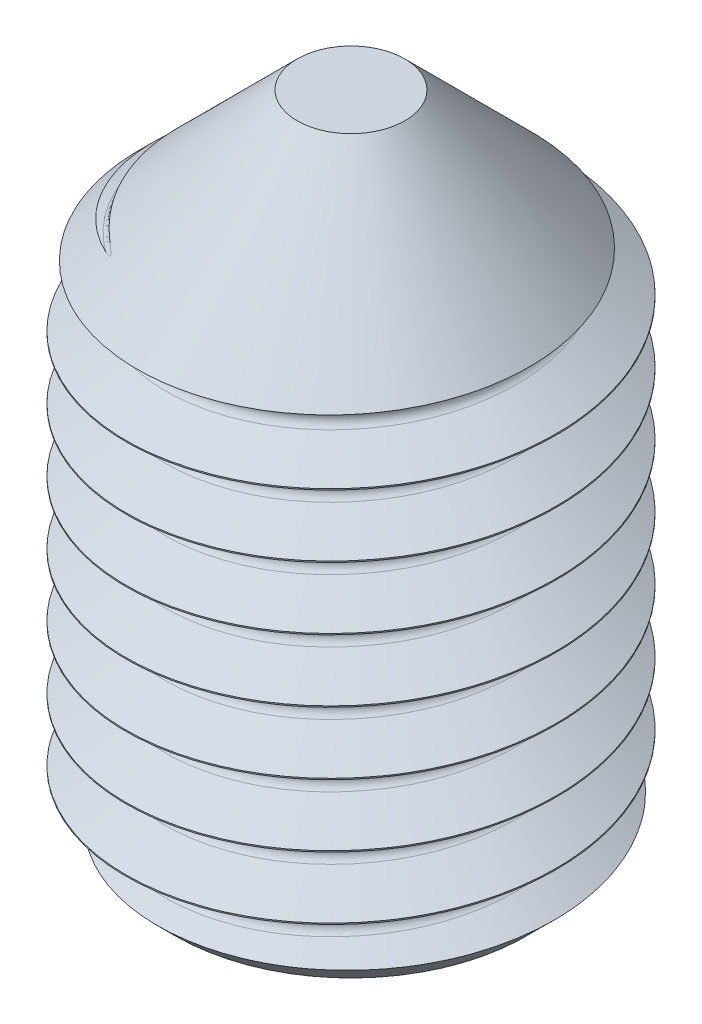
SolidWorks part; units mm, degrees
ref_plane "Front Plane" through (0, 0, 0) normal (0, 0, 1) x (1, 0, 0)
ref_plane "Top Plane" through (0, 0, 0) normal (0, 1, 0) x (1, 0, 0)
ref_plane "Right Plane" through (0, 0, 0) normal (1, 0, 0) x (0, 0, -1)
sketch "Sketch1" plane through (0, 0, 0) normal (0, 1, 0) x (1, 0, 0)
  circle A0 centre (0, 0) radius 6
  dimension "D1" = 12
extrude "Boss-Extrude1" add sketch "Sketch1" along normal mid plane 18
sketch "Sketch2" plane through (0, 0, 0) normal (0, 0, 1) x (1, 0, 0)
  line L0 (1.5, 9) -> (9.7582, 0.7418)
  line L1 (9.7582, 0.7418) -> (9.7582, -4.1418)
  line L2 (9.7582, -4.1418) -> (4.9, -9)
  line L3 (4.9, -9) -> (4.9, -11.4405)
  line L4 (4.9, -11.4405) -> (12.4714, -11.4405)
  line L5 (12.4714, -11.4405) -> (12.4714, 12.2044)
  line L6 (12.4714, 12.2044) -> (1.5, 12.2044)
  line L7 (1.5, 12.2044) -> (1.5, 9)
  line L8 (0, 0) -> (0, -3.1523) construction
  line L9 (6, 9) -> (-6, 9) construction
  line L10 (-6, -9) -> (6, -9) construction
  dimension "D1" = 3
  dimension "D2" = 9.8
  dimension "D3" = 135
  dimension "D4" = 135
revolve "Cut-Revolve1" cut sketch "Sketch2" angle 360 about L8
sketch "Sketch3" plane through (0, -9, 0) normal (0, -1, 0) x (1, 0, 0)
  line L1 (3.07, -1.7725) -> (3.07, 1.7725)
  line L2 (3.07, 1.7725) -> (0, 3.5449)
  line L3 (0, 3.5449) -> (-3.07, 1.7725)
  line L4 (-3.07, 1.7725) -> (-3.07, -1.7725)
  line L5 (-3.07, -1.7725) -> (0, -3.5449)
  line L6 (0, -3.5449) -> (3.07, -1.7725)
  circle A0 centre (0, 0) radius 3.07 construction
  dimension "D1" = 6.14
extrude "Cut-Extrude1" cut sketch "Sketch3" against normal blind 5.5
sketch "Sketch4" plane through (0, -9, 0) normal (0, -1, 0) x (1, 0, 0)
  circle A0 centre (0, 0) radius 6 construction
  circle A1 centre (0, 0) radius 6
curve "Helix/Spiral1" pitch 1.75 height 25.375 turns 14.5
sketch "Sketch5" plane through (0, 0, 0) normal (0, 0, 1) x (1, 0, 0)
  line L1 (6.0291, -8.4357) -> (4.8924, -9.0919)
  line L2 (4.8924, -9.5293) -> (6.0291, -10.1856)
  line L3 (6.0291, -10.1856) -> (6.0291, -8.4357)
  circle A0 centre (5.5239, -9.3106) radius 0.5052 construction
  arc A1 (4.8924, -9.0919) -> (4.8924, -9.5293) centre (5.0187, -9.3106) ccw
  point P7 (4.7598, -8.2039)
  point P8 (4.5964, -8.1574)
  point P9 (5.5852, -9.1676)
  point P10 (5.5239, -9.3106)
  dimension "D2" = 0.2525
  dimension "D1" = 1.7499
sweep "Cut-Sweep1" cut profiles "Sketch5" path "Helix/Spiral1" align with end faces yes
sketch "Sketch6" plane through (0, -9, 0) normal (0, -1, 0) x (1, 0, 0)
  circle A0 centre (0, 0) radius 3.5449
extrude "Cut-Extrude2" cut sketch "Sketch6" against normal blind 1.5 draft 75
